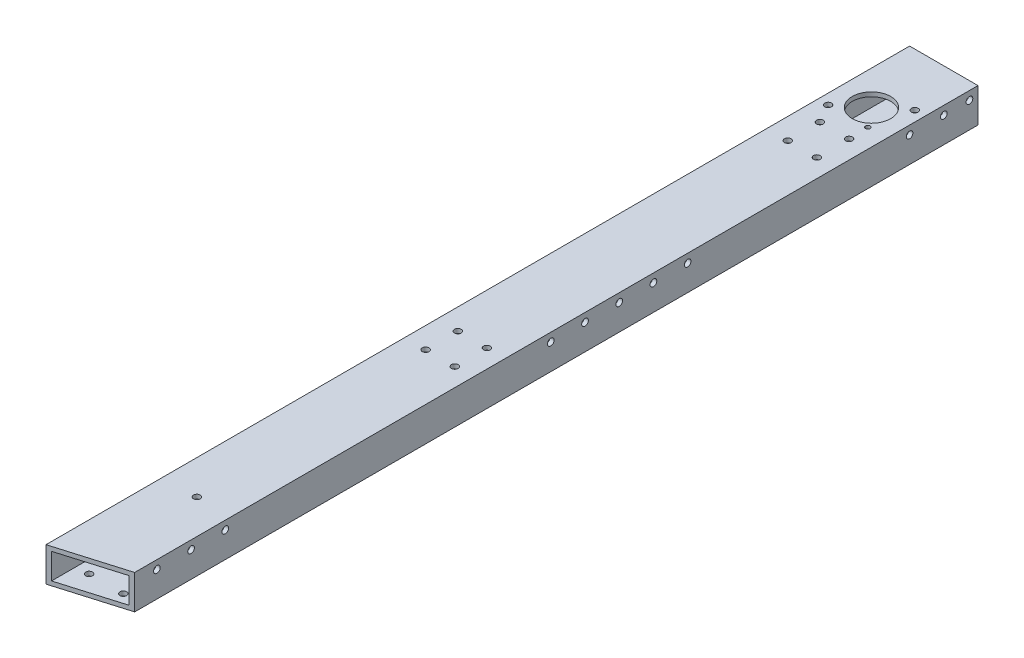
SolidWorks part; units mm, degrees
material "6061 Alloy"
ref_plane "Front Plane" through (0, 0, 0) normal (0, 0, 1) x (1, 0, 0)
ref_plane "Top Plane" through (0, 0, 0) normal (0, 1, 0) x (1, 0, 0)
ref_plane "Right Plane" through (0, 0, 0) normal (1, 0, 0) x (0, 0, -1)
sketch "Sketch1" plane through (0, 0, 0) normal (0, 0, 1) x (1, 0, 0)
  line L0 (-22.225, 9.525) -> (22.225, 9.525)
  line L2 (-25.4, 12.7) -> (25.4, 12.7)
  line L3 (-25.4, 12.7) -> (-25.4, -12.7)
  line L4 (-25.4, -12.7) -> (25.4, -12.7)
  line L5 (25.4, 12.7) -> (25.4, -12.7)
  line L10 (22.225, 9.525) -> (22.225, -9.525)
  line L11 (-22.225, -9.525) -> (22.225, -9.525)
  line L12 (-22.225, 9.525) -> (-22.225, -9.525)
  point P12 (0, 12.7)
  point P14 (25.4, 0)
  dimension "Wall Thickness" = 3.175
  dimension "Outside Width" = 50.8
  dimension "Outside Height" = 25.4
  dimension "Inside Height" = 19.05
  dimension "Inside Width" = 44.45
sketch "Sketch2" plane through (0, 0, 0) normal (1, 0, 0) x (0, 0, -1)
  line L0 (320.675, 0) -> (-320.675, 0)
  point P4 (0, 0)
  point P7 (-320.675, 0)
  point P10 (320.675, 0)
  dimension "Length" = 641.35
sketch "Sketch3" plane through (0, 0, 0) normal (0, 0, 1) x (1, 0, 0)
  line L21 (25.4, 12.7) -> (-25.4, 12.7)
  line L22 (25.4, -12.7) -> (25.4, 12.7)
  line L23 (-25.4, -12.7) -> (25.4, -12.7)
  line L24 (-25.4, 12.7) -> (-25.4, -12.7)
  line L25 (25.4, 12.7) -> (-25.4, 12.7)
  line L26 (25.4, -12.7) -> (25.4, 12.7)
  line L27 (-25.4, -12.7) -> (25.4, -12.7)
  line L28 (-25.4, 12.7) -> (-25.4, -12.7)
  line L29 (22.225, 9.525) -> (-22.225, 9.525)
  line L30 (22.225, -9.525) -> (22.225, 9.525)
  line L31 (-22.225, -9.525) -> (22.225, -9.525)
  line L32 (-22.225, 9.525) -> (-22.225, -9.525)
  line L33 (22.225, 9.525) -> (-22.225, 9.525)
  line L34 (22.225, -9.525) -> (22.225, 9.525)
  line L35 (-22.225, -9.525) -> (22.225, -9.525)
  line L36 (-22.225, 9.525) -> (-22.225, -9.525)
  dimension "D1" = 0
  dimension "D2" = 0
extrude "Boss-Extrude1" add sketch "Sketch3" along normal up to vertex (320.675 mm away) and the other way up to vertex (320.675 mm away) up to point (0, 0, 320.675) other way up to point (0, 0, -320.675)
sketch "Drawing Reference" plane through (0, 0, 0) normal (1, 0, 0) x (0, 0, -1)
  line L0 (-320.675, 0) -> (320.675, 0) construction
  line L1 (0, -12.7) -> (0, 12.7) construction
  line L2 (-320.675, -12.7) -> (320.675, -12.7) construction
  line L5 (-320.675, 12.7) -> (320.675, 12.7) construction
  point P7 (-284.099, 0)
  point P8 (284.099, 0)
  dimension "D1" = 36.576
sketch "Sketch4" plane through (0, 12.7, 0) normal (0, 1, 0) x (1, 0, 0)
  line L0 (-25.4, -320.675) -> (25.4, -305.6274)
  line L1 (25.4, -320.675) -> (25.4, 320.675) construction
  line L2 (25.4, -320.675) -> (-25.4, -320.675)
  dimension "D1" = 16.5
extrude "Cut-Extrude1" cut sketch "Sketch4" against normal through all and the other way through all flip side to cut
sketch "Sketch8" plane through (0, 12.7, 0) normal (0, 1, 0) x (1, 0, 0)
  line L0 (0, 320.675) -> (0, 266.954) construction
  line L1 (25.4, 320.675) -> (-25.4, 320.675) construction
  circle A0 centre (0, 266.954) radius 14.2875
  dimension "D1" = 53.721
extrude "Cut-Extrude2" cut sketch "Sketch8" against normal through all
sketch "Sketch9" plane through (0, -12.7, 0) normal (0, -1, 0) x (1, 0, 0)
  line L0 (-12.7762, 284.753) -> (-12.7762, 301.263) construction
  line L1 (-12.7762, 301.263) -> (12.6238, 301.263) construction
  line L2 (12.6238, 301.263) -> (12.6238, 284.753) construction
  line L3 (12.6238, 284.753) -> (-12.7762, 284.753) construction
hole_wizard "#10 Clearance Hole1" positions "Sketch10" profile "Sketch11" hole size "#10" standard "ANSI Inch"
sketch "Sketch10" plane through (0, -12.7, 0) normal (0, -1, 0) x (-1, 0, 0)
  point P0 (-12.6238, -284.753)
  point P3 (12.7762, -284.753)
  point P6 (12.7762, -301.263)
  point P9 (-12.6238, -301.263)
sketch "Sketch11" plane through (12.6238, -12.7, 284.753) normal (1, 0, 0) x (0, 0, -1)
  line L0 (0, 0) -> (0, 6.5757)
  line L1 (0, 6.5757) -> (2.4892, 5.08)
  line L2 (2.4892, 5.08) -> (2.4892, 0)
  line L5 (2.4892, 0) -> (0, 0)
  line L10 (0, 6.5757) -> (-2.4892, 5.08) construction
  line L11 (0, -6.35) -> (0, 107.95) construction
  dimension "Hole Dia." = 4.9784
  dimension "Hole Depth" = 5.08
  dimension "Drill Angle" = 118
sketch "Sketch12" plane through (25.4, 0, 0) normal (1, 0, 0) x (0, 0, -1)
  line L0 (320.675, 533.4) -> (-305.6274, 533.4) construction
  line L1 (320.675, 520.7) -> (320.675, 546.1) construction
  line L2 (-305.6274, 546.1) -> (-305.6274, 520.7) construction
hole_wizard "#10 Clearance Hole2" positions "Sketch13" profile "Sketch14" hole size "#10" standard "ANSI Inch" end condition through all
sketch "Sketch13" plane through (25.4, 0, 0) normal (1, 0, 0) x (0, 0, -1)
  point P0 (314.325, 6.35)
  point P3 (295.275, 6.35)
sketch "Sketch14" plane through (25.4, 6.35, -314.325) normal (0, 1, 0) x (0, 0, -1)
  line L0 (0, 0) -> (0, 50.8)
  line L1 (0, 50.8) -> (2.4892, 50.8)
  line L2 (2.4892, 50.8) -> (2.4892, 0)
  line L5 (2.4892, 0) -> (0, 0)
  line L11 (0, -6.35) -> (0, 107.95) construction
  dimension "Thru Hole Dia." = 4.9784
  dimension "Thru Hole Depth" = 50.8
hole_wizard "#10 Clearance Hole3" positions "Sketch15" profile "Sketch16" hole size "#10" standard "ANSI Inch" end condition through all
sketch "Sketch15" plane through (25.4, 0, 0) normal (1, 0, 0) x (0, 0, -1)
  point P0 (105.029, 6.35)
  point P3 (79.629, 6.35)
  point P6 (54.229, 6.35)
  point P9 (28.829, 6.35)
  point P12 (3.429, 6.35)
  point P24 (-289.1267, 6.3882)
  point P27 (-263.7267, 6.3882)
  point P30 (-238.3267, 6.3882)
sketch "Sketch16" plane through (25.4, 6.35, -105.029) normal (0, 1, 0) x (0, 0, -1)
  line L0 (0, 0) -> (0, 50.8)
  line L1 (0, 50.8) -> (2.4892, 50.8)
  line L2 (2.4892, 50.8) -> (2.4892, 0)
  line L5 (2.4892, 0) -> (0, 0)
  line L11 (0, -6.35) -> (0, 107.95) construction
  dimension "Thru Hole Dia." = 4.9784
  dimension "Thru Hole Depth" = 50.8
sketch "Sketch18" plane through (0, 12.7, 0) normal (0, 1, 0) x (1, 0, 0)
  line L0 (-17.786, 252.537) -> (17.786, 281.371) construction
  line L1 (0, 266.954) -> (11.3559, 252.9444) construction
hole_wizard "#10 Clearance Hole4" positions "Sketch19" profile "Sketch20" hole size "#10" standard "ANSI Inch"
sketch "Sketch19" plane through (0, 12.7, 0) normal (0, 1, 0) x (1, 0, 0)
  point P0 (17.786, 281.371)
  point P3 (-17.786, 252.537)
sketch "Sketch20" plane through (17.786, 12.7, -281.371) normal (1, 0, 0) x (0, 0, 1)
  line L0 (0, 0) -> (0, 6.5757)
  line L1 (0, 6.5757) -> (2.4892, 5.08)
  line L2 (2.4892, 5.08) -> (2.4892, 0)
  line L5 (2.4892, 0) -> (0, 0)
  line L10 (0, 6.5757) -> (-2.4892, 5.08) construction
  line L11 (0, -6.35) -> (0, 107.95) construction
  dimension "Hole Dia." = 4.9784
  dimension "Hole Depth" = 5.08
  dimension "Drill Angle" = 118
sketch "Sketch21" plane through (0, 12.7, 0) normal (0, 1, 0) x (1, 0, 0)
  line L0 (-0.0762, -284.753) -> (-0.0762, -233.953) construction
  line L1 (12.6238, -284.753) -> (-12.7762, -284.753) construction
  dimension "D1" = 50.8
hole_wizard "#10 Clearance Hole5" positions "Sketch22" profile "Sketch23" hole size "#10" standard "ANSI Inch" end condition through all
sketch "Sketch22" plane through (0, 12.7, 0) normal (0, 1, 0) x (1, 0, 0)
  point P0 (-0.0762, -233.953)
sketch "Sketch23" plane through (-0.0762, 12.7, 233.953) normal (1, 0, 0) x (0, 0, 1)
  line L0 (0, 0) -> (0, 25.4)
  line L1 (0, 25.4) -> (2.4892, 25.4)
  line L2 (2.4892, 25.4) -> (2.4892, 0)
  line L5 (2.4892, 0) -> (0, 0)
  line L11 (0, -6.35) -> (0, 107.95) construction
  dimension "Thru Hole Dia." = 4.9784
  dimension "Thru Hole Depth" = 25.4
hole_wizard "Tap Drill for #8-32 Tap1" positions "Sketch24" profile "Sketch25" hole size "#8-32" standard "ANSI Inch"
sketch "Sketch24" plane through (0, 12.7, 0) normal (0, 1, 0) x (1, 0, 0)
  point P0 (11.3559, 252.9444)
sketch "Sketch25" plane through (11.3559, 12.7, -252.9444) normal (1, 0, 0) x (0, 0, 1)
  line L0 (0, 0) -> (0, 6.1178)
  line L1 (0, 6.1178) -> (1.7272, 5.08)
  line L2 (1.7272, 5.08) -> (1.7272, 0)
  line L5 (1.7272, 0) -> (0, 0)
  line L10 (0, 6.1178) -> (-1.7272, 5.08) construction
  line L11 (0, -6.35) -> (0, 107.95) construction
  dimension "Hole Dia." = 3.4544
  dimension "Hole Depth" = 5.08
  dimension "Drill Angle" = 118
hole_wizard "#10 Clearance Hole6" positions "Sketch26" profile "Sketch27" hole size "#10" standard "ANSI Inch" end condition through all
sketch "Sketch26" plane through (0, 12.7, 0) normal (0, 1, 0) x (1, 0, 0)
  point P0 (-9.7957, 238.4742)
  point P3 (11.8451, 238.4742)
  point P6 (11.8451, 214.5982)
  point P9 (-9.7957, 214.5982)
  point P12 (11.8451, -30.4483)
  point P15 (-9.7957, -30.4483)
  point P18 (-9.7957, -54.3243)
  point P21 (11.8451, -54.3243)
sketch "Sketch27" plane through (-9.7957, 12.7, -238.4742) normal (1, 0, 0) x (0, 0, 1)
  line L0 (0, 0) -> (0, 25.4)
  line L1 (0, 25.4) -> (5.2197, 25.4)
  line L2 (2.4892, 22.2589) -> (2.4892, 0)
  line L5 (2.4892, 0) -> (0, 0)
  line L7 (5.2197, 25.4) -> (2.4892, 22.2589)
  line L8 (-5.2197, 25.4) -> (-2.4892, 22.2589) construction
  line L11 (0, -6.35) -> (0, 107.95) construction
  dimension "Thru Hole Dia." = 4.9784
  dimension "Thru Hole Depth" = 25.4
  dimension "Far C'Sink Dia." = 10.4394
  dimension "Far C'Sink Angle" = 82
hole_wizard "#10 (0.1935) Diameter Hole1" positions "Sketch28" profile "Sketch29" hole size "#10" standard "ANSI Inch"
sketch "Sketch28" plane through (25.4, 0, 0) normal (1, 0, 0) x (0, 0, -1)
  point P5 (269.875, 6.35)
sketch "Sketch29" plane through (25.4, 6.35, -269.875) normal (0, 1, 0) x (0, 0, -1)
  line L0 (0, 0) -> (0, 4.7786)
  line L1 (0, 4.7786) -> (2.4574, 3.302)
  line L2 (2.4574, 3.302) -> (2.4574, 0)
  line L5 (2.4574, 0) -> (0, 0)
  line L10 (0, 4.7786) -> (-2.4574, 3.302) construction
  line L11 (0, -6.35) -> (0, 107.95) construction
  dimension "Hole Dia." = 4.9149
  dimension "Hole Depth" = 3.302
  dimension "Drill Angle" = 118
equation "\"D1@Drawing Reference\"=\"Outside Width@Sketch1\" * 0.72"
